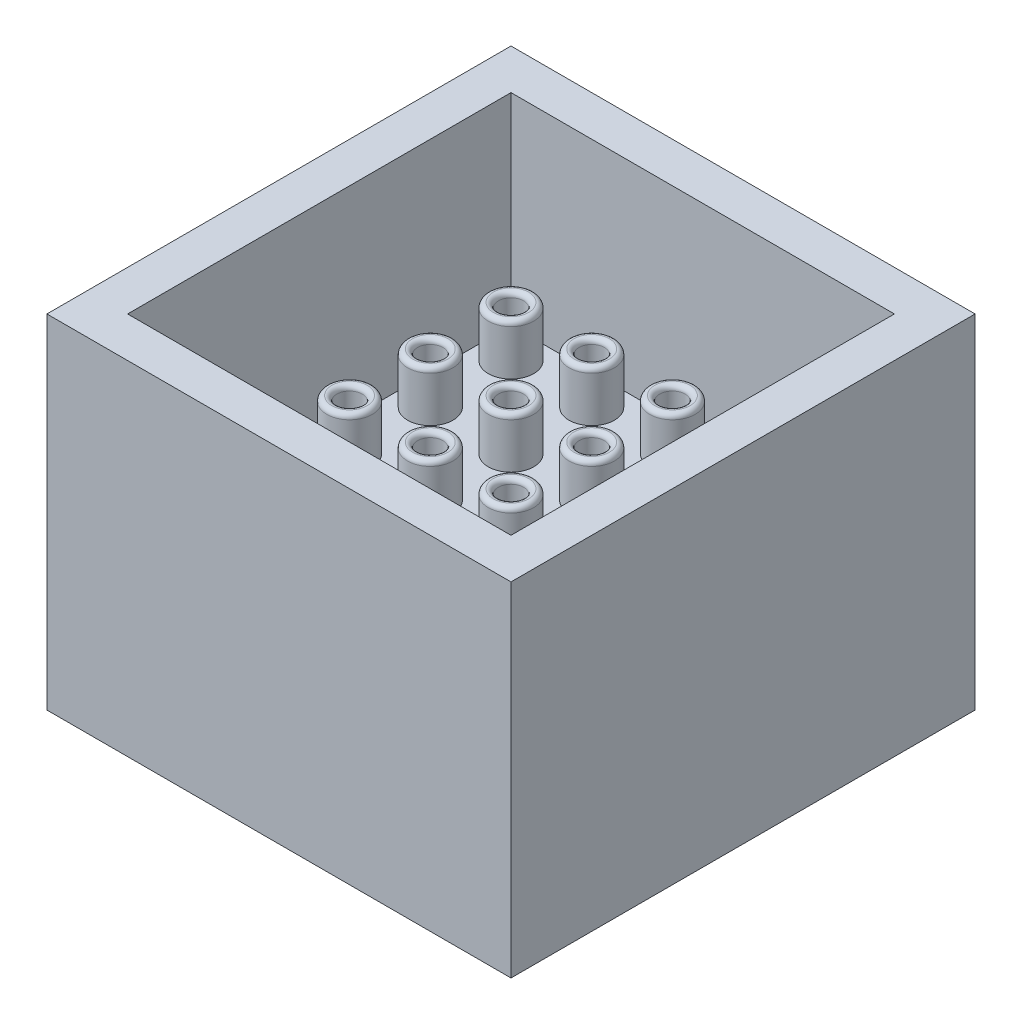
SolidWorks part; units mm, degrees
ref_plane "Front Plane" through (0, 0, 0) normal (0, 0, 1) x (1, 0, 0)
ref_plane "Top Plane" through (0, 0, 0) normal (0, 1, 0) x (1, 0, 0)
ref_plane "Right Plane" through (0, 0, 0) normal (1, 0, 0) x (0, 0, -1)
sketch "Sketch1" plane through (0, 0, 0) normal (0, 1, 0) x (1, 0, 0)
  line L0 (-11.5, 11.5) -> (11.5, 11.5)
  line L1 (-9.5, -9.5) -> (9.5, -9.5)
  line L2 (-9.5, -9.5) -> (-9.5, 9.5)
  line L3 (-9.5, 9.5) -> (9.5, 9.5)
  line L4 (9.5, -9.5) -> (9.5, 9.5)
  line L5 (-9.5, -9.5) -> (9.5, 9.5) construction
  line L6 (-9.5, 9.5) -> (9.5, -9.5) construction
  line L7 (11.5, -11.5) -> (11.5, 11.5)
  line L8 (-11.5, -11.5) -> (11.5, -11.5)
  line L9 (-11.5, -11.5) -> (-11.5, 11.5)
  point P0 (0, 0)
  dimension "D1" = 19
  dimension "D2" = 2
extrude "Boss-Extrude1" add sketch "Sketch1" along normal blind 10
sketch "Sketch2" plane through (0, 0, 0) normal (0, -1, 0) x (1, 0, 0)
  line L1 (-11.5, 11.5) -> (11.5, 11.5)
  line L2 (-11.5, 11.5) -> (-11.5, -11.5)
  line L3 (-11.5, -11.5) -> (11.5, -11.5)
  line L4 (11.5, 11.5) -> (11.5, -11.5)
  line L5 (-11.5, 11.5) -> (11.5, -11.5) construction
  line L6 (-11.5, -11.5) -> (11.5, 11.5) construction
  point P0 (0, 0)
extrude "Boss-Extrude2" add sketch "Sketch2" along normal blind 2
sketch "Sketch3" plane through (0, -2, 0) normal (0, -1, 0) x (1, 0, 0)
  line L0 (-9.5, 9.5) -> (9.5, 9.5)
  line L1 (-11.5, -11.5) -> (11.5, -11.5)
  line L2 (-11.5, -11.5) -> (-11.5, 11.5)
  line L3 (-11.5, 11.5) -> (11.5, 11.5)
  line L4 (11.5, -11.5) -> (11.5, 11.5)
  line L5 (-11.5, -11.5) -> (11.5, 11.5) construction
  line L6 (-11.5, 11.5) -> (11.5, -11.5) construction
  line L7 (9.5, -9.5) -> (9.5, 9.5)
  line L8 (-9.5, -9.5) -> (9.5, -9.5)
  line L9 (-9.5, -9.5) -> (-9.5, 9.5)
  point P0 (0, 0)
  dimension "D1" = 2
extrude "Boss-Extrude3" add sketch "Sketch3" along normal blind 5
sketch "Sketch6" plane through (0, 0, 0) normal (0, 1, 0) x (1, 0, 0)
  line L0 (9.5, -9.5) -> (9.5, 9.5) construction
  line L1 (9.5, 9.5) -> (-9.5, 9.5) construction
  circle A0 centre (8, 8) radius 1.125
  dimension "D2" = 2.25
  dimension "D1" = 1.5
  dimension "D3" = 1.5
extrude "Boss-Extrude5" add sketch "Sketch6" along normal blind 2.5
sketch "Sketch7" plane through (0, 2.5, 0) normal (0, 1, 0) x (1, 0, 0)
  circle A0 centre (8, 8) radius 0.625
  dimension "D1" = 1.25
extrude "Cut-Extrude2" cut sketch "Sketch7" against normal up to next
fillet "Fillet3" radius 0.25 2 edges at (8, 2.5, -6.875) (8, 2.5, -7.375)
pattern_linear "LPattern1" count 5 spacing 4 along (0, 0, 1) count 5 spacing 4 along (-1, 0, 0) of "Boss-Extrude5", "Cut-Extrude2", "Fillet3"
